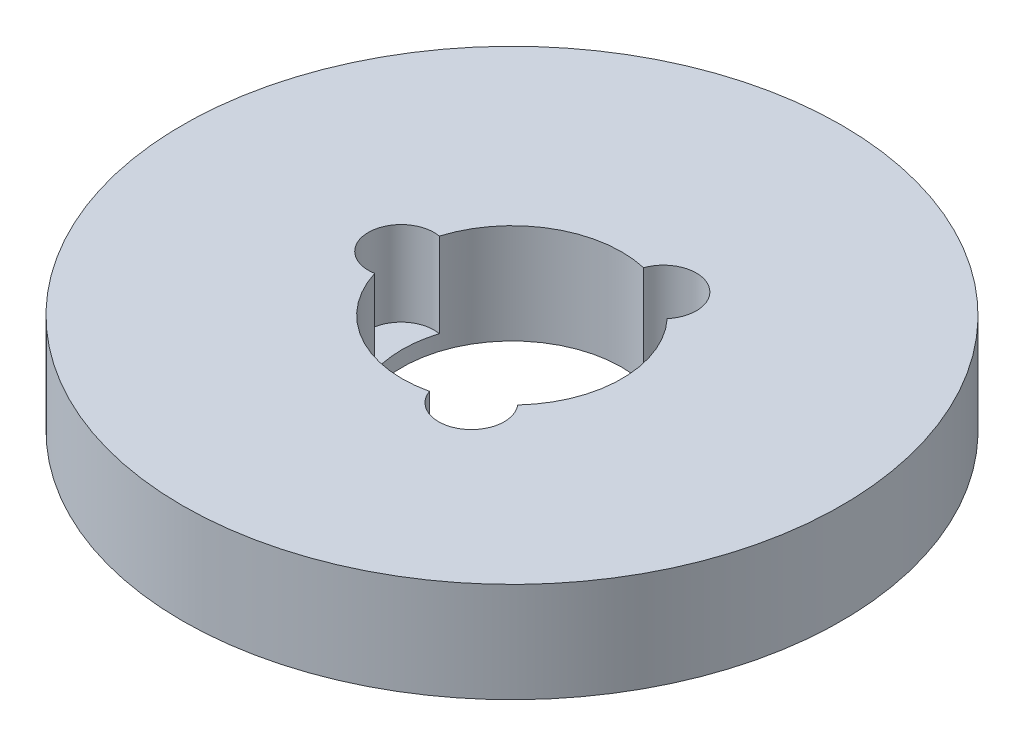
SolidWorks part; units mm, degrees
ref_plane "Front Plane" through (0, 0, 0) normal (0, 0, 1) x (1, 0, 0)
ref_plane "Top Plane" through (0, 0, 0) normal (0, 1, 0) x (1, 0, 0)
ref_plane "Right Plane" through (0, 0, 0) normal (1, 0, 0) x (0, 0, -1)
sketch "Sketch1" plane through (0, 0, 0) normal (0, 1, 0) x (1, 0, 0)
  circle A0 centre (0, 0) radius 82.5
  dimension "FLANGE_OD" = 165
extrude "Boss-Extrude1" add sketch "Sketch1" along normal blind 25
sketch "Sketch2" plane through (0, 0, 0) normal (0, 1, 0) x (1, 0, 0)
  circle A0 centre (0, 0) radius 27.5
  dimension "BORE_D" = 55
extrude "Cut-Extrude1" cut sketch "Sketch2" along normal through all
sketch "Sketch3" plane through (0, 25, 0) normal (0, 1, 0) x (1, 0, 0)
  circle A0 centre (0, 0) radius 27.753 construction
  circle A1 centre (-27.753, 0) radius 8.2195
  dimension "BOLT_D" = 16.439
  dimension "BOLT_PCD" = 55.506
extrude "Cut-Extrude2" cut sketch "Sketch3" against normal blind 21.1538
pattern_circular "CirPattern1" count 3 over 360 about axis through (0, 0, 0) along (0, 1, 0) of "Cut-Extrude2"
